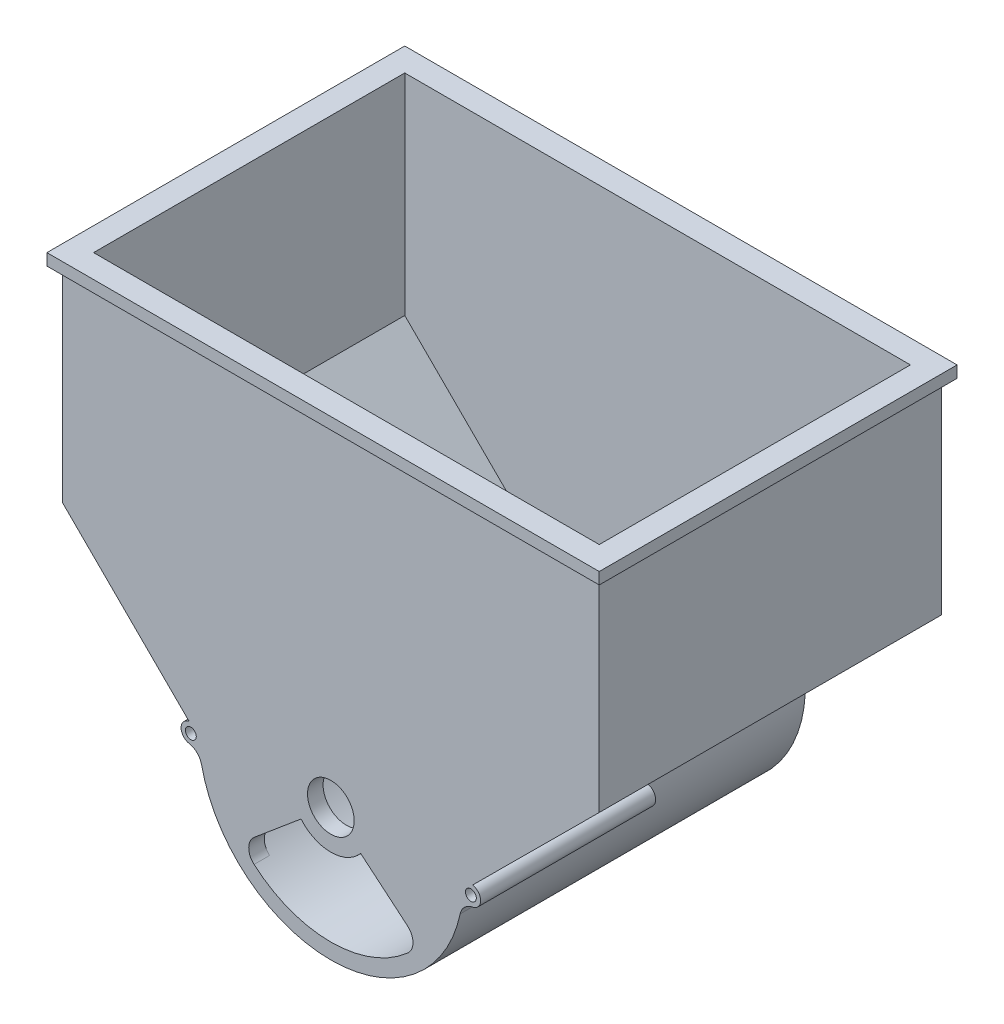
SolidWorks part; units mm, degrees
ref_plane "前基準面" through (0, 0, 0) normal (0, 0, 1) x (1, 0, 0)
ref_plane "上基準面" through (0, 0, 0) normal (0, 1, 0) x (1, 0, 0)
ref_plane "右基準面" through (0, 0, 0) normal (1, 0, 0) x (0, 0, -1)
sketch "草圖1" plane through (0, 0, 0) normal (0, 0, 1) x (1, 0, 0)
  line L0 (65, 50) -> (65, -35) construction
  line L2 (0, 0) -> (0, 50)
  line L3 (0, 50) -> (130, 50)
  line L4 (130, 0) -> (130, 50)
  line L5 (0, 0) -> (35.0004, -34.8465)
  line L6 (130, 0) -> (94.9996, -34.8465)
  line L7 (-4, -1.662) -> (-4, 54)
  line L8 (-4, 54) -> (134, 54)
  line L9 (134, -1.662) -> (134, 54)
  line L10 (134, -1.662) -> (98.965, -36.543)
  line L11 (-4, -1.662) -> (31.035, -36.543)
  arc A0 (35.0004, -34.8465) -> (94.9996, -34.8465) centre (65, -35) ccw
  arc A1 (31.035, -36.543) -> (98.965, -36.543) centre (65, -35) ccw
  dimension "D4" = 60
  dimension "D1" = 130
  dimension "D2" = 50
  dimension "D3" = 85
  dimension "D5" = 4
  dimension "D6" = 50
extrude "填料-伸長1" add sketch "草圖1" along normal blind 80
sketch "草圖2" plane through (0, 0, 80) normal (0, 0, 1) x (1, 0, 0)
  line L5 (-4, 54) -> (-4, -1.662)
  line L6 (134, 54) -> (-4, 54)
  line L7 (134, -1.662) -> (134, 54)
  line L8 (98.965, -36.543) -> (134, -1.662)
  line L9 (-4, -1.662) -> (31.035, -36.543)
  line L10 (-4, 54) -> (-4, -1.662)
  line L11 (134, 54) -> (-4, 54)
  line L12 (134, -1.662) -> (134, 54)
  line L13 (98.965, -36.543) -> (134, -1.662)
  line L14 (-4, -1.662) -> (31.035, -36.543)
  line L15 (0, 50) -> (0, 0)
  line L16 (130, 50) -> (0, 50)
  line L17 (130, 0) -> (130, 50)
  line L18 (94.9996, -34.8465) -> (130, 0)
  line L19 (0, 0) -> (35.0004, -34.8465)
  arc A1 (31.035, -36.543) -> (98.965, -36.543) centre (65, -35) ccw
  arc A2 (31.035, -36.543) -> (98.965, -36.543) centre (65, -35) ccw
  arc A3 (35.0004, -34.8465) -> (94.9996, -34.8465) centre (65, -35) ccw
  arc A4 (35.0004, -34.8465) -> (94.9996, -34.8465) centre (65, -35) ccw
  line M13 (-4, -1.662) -> (31.035, -36.543)
  arc M14 (31.035, -36.543) -> (98.965, -36.543) centre (65, -35) ccw
  line M15 (98.965, -36.543) -> (134, -1.662)
  line M16 (134, -1.662) -> (134, 54)
  line M17 (134, 54) -> (-4, 54)
  line M18 (-4, 54) -> (-4, -1.662)
  arc M19 (94.9996, -34.8465) -> (35.0004, -34.8465) centre (65, -35) cw
  line M20 (35.0004, -34.8465) -> (0, 0)
  line M21 (0, 0) -> (0, 50)
  line M22 (0, 50) -> (130, 50)
  line M23 (130, 50) -> (130, 0)
  line M24 (130, 0) -> (94.9996, -34.8465)
  dimension "D1" = 0
  dimension "D2" = 0
extrude "填料-伸長2" add sketch "草圖2" along normal blind 4 contours M18 M13 M14 M15 M16 M17 M24 M19 M20 M21 M22 M23 | M19 M24 M23 M22 M21 M20 region at (65, 52.1514, 80) region at (65, 3.9261, 80)
sketch "草圖3" plane through (0, 0, 0) normal (0, 0, -1) x (-1, 0, 0)
  line L5 (4, -1.662) -> (4, 54)
  line L6 (-31.035, -36.543) -> (4, -1.662)
  line L7 (-134, -1.662) -> (-98.965, -36.543)
  line L8 (-134, 54) -> (-134, -1.662)
  line L9 (4, 54) -> (-134, 54)
  line L10 (4, -1.662) -> (4, 54)
  line L11 (-31.035, -36.543) -> (4, -1.662)
  line L12 (-134, -1.662) -> (-98.965, -36.543)
  line L13 (-134, 54) -> (-134, -1.662)
  line L14 (4, 54) -> (-134, 54)
  arc A0 (-94.9996, -34.8465) -> (-35.0004, -34.8465) centre (-65, -35) ccw construction
  arc A1 (-98.965, -36.543) -> (-31.035, -36.543) centre (-65, -35) ccw
  arc A2 (-98.965, -36.543) -> (-31.035, -36.543) centre (-65, -35) ccw
  arc A3 (-94.9996, -34.8465) -> (-35.0004, -34.8465) centre (-65, -35) ccw
  line M7 (-31.035, -36.543) -> (4, -1.662)
  line M8 (4, -1.662) -> (4, 54)
  line M9 (4, 54) -> (-134, 54)
  line M10 (-134, 54) -> (-134, -1.662)
  line M11 (-134, -1.662) -> (-98.965, -36.543)
  arc M12 (-98.965, -36.543) -> (-31.035, -36.543) centre (-65, -35) ccw
  line M13 (0, 0) -> (-35.0004, -34.8465)
  arc M14 (-35.0004, -34.8465) -> (-94.9996, -34.8465) centre (-65, -35) cw
  line M15 (-94.9996, -34.8465) -> (-130, 0)
  line M16 (-130, 0) -> (-130, 50)
  line M17 (-130, 50) -> (0, 50)
  line M18 (0, 50) -> (0, 0)
  dimension "D1" = 0
extrude "填料-伸長3" add sketch "草圖3" along normal blind 4 contours M13 M18 M17 M16 M15 M14 | M12 M7 M8 M9 M10 M11 M18 M13 M14 M15 M16 M17 region at (14.8218, -17.7925, 0) region at (65, 3.9261, 0)
sketch "草圖4" plane through (0, 54, 0) normal (0, 1, 0) x (1, 0, 0)
  line L0 (-4, -84) -> (-4, 4) construction
  line L1 (-4, 4) -> (134, 4)
  line L2 (-4, 4) -> (-4, -84)
  line L3 (-4, -84) -> (134, -84)
  line L4 (134, 4) -> (134, -84)
  line L5 (-4, 4) -> (134, 4) construction
  line L6 (0, 0) -> (130, 0)
  line L7 (130, 0) -> (130, -80)
  line L8 (0, -80) -> (130, -80)
  line L9 (0, 0) -> (0, -80)
  dimension "D1" = 4
extrude "除料-伸長1" cut sketch "草圖4" against normal blind 4 contours L6 L9 L8 L7 region at (65, 54, 40)
sketch "草圖5" plane through (0, 0, 84) normal (0, 0, 1) x (1, 0, 0)
  line L0 (65, 54) -> (65, -69) construction
  line L1 (134, 54) -> (-4, 54) construction
  arc A0 (31.035, -36.543) -> (98.965, -36.543) centre (65, -35) ccw construction
  circle A1 centre (65, -35) radius 6
  dimension "D1" = 12
extrude "除料-伸長2" cut sketch "草圖5" against normal up to surface (88 mm away) up to face at (65, -0.1445, -4)
sketch "草圖6" plane through (0, 0, 84) normal (0, 0, 1) x (1, 0, 0)
  line L0 (65, -35) -> (42.0187, -54.2836)
  line L1 (65, -35) -> (87.9813, -54.2836)
  line L2 (65, 54) -> (65, -69) construction
  line L3 (134, 54) -> (-4, 54) construction
  arc A0 (42.0187, -54.2836) -> (87.9813, -54.2836) centre (65, -35) ccw
  arc A1 (31.035, -36.543) -> (98.965, -36.543) centre (65, -35) ccw construction
  arc A2 (57.3396, -41.4279) -> (72.6604, -41.4279) centre (65, -35) ccw
  dimension "D1" = 4
  dimension "D2" = 20
  dimension "D3" = 50
  dimension "D4" = 50
extrude "除料-伸長3" cut sketch "草圖6" against normal up to surface (4 mm away) contours L2 A2 L0 A0 | A2 L2 A0 L1 region at (56.1311, -54.0195, 84) region at (73.8689, -54.0195, 84) up to face at (71, -35, 80)
sketch "草圖7" plane through (0, 0, -4) normal (0, 0, -1) x (-1, 0, 0)
  line L0 (-65, 54) -> (-65, -69) construction
  line L1 (4, 54) -> (-134, 54) construction
  circle A0 centre (-65, -43) radius 21
  circle A1 centre (-65, -35) radius 6 construction
  arc A2 (-98.965, -36.543) -> (-31.035, -36.543) centre (-65, -35) ccw construction
  dimension "D1" = 42
  dimension "D2" = 8
extrude "填料-伸長4" add sketch "草圖7" along normal blind 1
sketch "草圖9" plane through (0, 0, -5) normal (0, 0, -1) x (-1, 0, 0)
  line L0 (-65, -22) -> (-65, -64) construction
  line L1 (-86, -43) -> (-44, -43) construction
  circle A0 centre (-65, -35) radius 4.6
  circle A1 centre (-65, -43) radius 21
  circle A2 centre (-65, -43) radius 21
  circle A3 centre (-82.5, -43) radius 1.35
  circle A4 centre (-47.5, -43) radius 1.35
  dimension "D2" = 9.2
  dimension "D3" = 2.7
  dimension "D4" = 17.5
  dimension "D5" = 8
  dimension "D1" = 0
extrude "除料-伸長5" cut sketch "草圖9" against normal up to next contours A0 | A3 | A4 region at (65, -35, -5) region at (82.5, -43, -5) region at (47.5, -43, -5)
ref_plane "平面1" through (65, 0, 0) normal (1, 0, 0) x (0, 0, -1)
sketch "草圖10" plane through (65, 0, 0) normal (1, 0, 0) x (0, 0, -1)
  line L0 (-84, -69) -> (-84, 0) construction
  line L1 (-84, 28.7653) -> (-59, 1)
  line L3 (-84, 1) -> (-84, 28.7653)
  line L4 (-83, 26.1602) -> (-60.3456, 1)
  line L5 (-60.3456, 1) -> (-83, 1)
  line L6 (-83, 1) -> (-83, 26.1602)
  line L7 (-83, 1) -> (-84, 1)
  line L8 (-60.3456, 1) -> (-59, 1)
  line L9 (-84, 28.7653) -> (-58.0996, 0) construction
  line L10 (-58.0996, 0) -> (-84, 0) construction
  line L11 (-84, 1) -> (-84, 71.0976) construction
  line L12 (-84, 0) -> (-84, 28.7653) construction
  line L14 (-84, -1.662) -> (-84, 54) construction
  dimension "D1" = 1
  dimension "D2" = 42
  dimension "D3" = 70
  dimension "D4" = 25
extrude "填料-伸長5" add sketch "草圖10" along normal up to surface and the other way up to surface contours L4 L8 L1 L3 L7 L6 region at (65, 14.6327, 71.7777) up to face at (130, 27, 40) other way up to face at (0, 27, 40)
sketch "草圖11" plane through (0, 0, 84) normal (0, 0, 1) x (1, 0, 0)
  line L0 (-4, -1.662) -> (31.035, -36.543)
  line L1 (31.035, -36.543) -> (-4, -36.543)
  line L2 (-4, -36.543) -> (-4, -1.662)
  line L3 (134, -1.662) -> (98.965, -36.543)
  line L4 (98.965, -36.543) -> (134, -36.543)
  line L5 (134, -36.543) -> (134, -1.662)
extrude "除料-伸長6" [suppressed] cut sketch "草圖11" against normal up to surface (88 mm away)
sketch "草圖12" plane through (0, 54, 0) normal (0, 1, 0) x (1, 0, 0)
  line L0 (-4, -84) -> (-4, 4) construction
  line L1 (-6, 6) -> (136, 6)
  line L2 (-6, 6) -> (-6, -86)
  line L3 (-6, -86) -> (136, -86)
  line L4 (136, 6) -> (136, -86)
  line L5 (-4, 4) -> (134, 4) construction
  line L6 (134, -84) -> (134, 4) construction
  line L7 (134, -84) -> (-4, -84) construction
  line L9 (-4, 4) -> (134, 4)
  line L10 (-4, 4) -> (-4, -84)
  line L11 (-4, -84) -> (134, -84)
  line L12 (134, 4) -> (134, -84)
  dimension "D1" = 2
  dimension "D2" = 2
  dimension "D3" = 2
  dimension "D4" = 2
extrude "填料-伸長6" add sketch "草圖12" against normal blind 3
chamfer "導角1" distance 1 angle 45 1 edges at (44, -43, -4)
sketch "草圖13" plane through (0, 0, 84) normal (0, 0, 1) x (1, 0, 0)
  line L0 (31.035, -36.543) -> (98.965, -36.543) construction
  line L1 (29, -36.543) -> (101, -36.543) construction
  line L2 (65, -69) -> (65, 51) construction
  line L3 (-4, 51) -> (134, 51) construction
  arc A0 (29.0868, -34.0445) -> (29.0272, -35.1432) centre (65, -36.543) ccw
  circle A2 centre (29, -36.543) radius 2.5
  circle A3 centre (29, -36.543) radius 1.4
  arc A4 (29.0272, -37.9427) -> (101, -36.543) centre (65, -36.543) ccw
  arc A5 (31.035, -36.543) -> (98.965, -36.543) centre (65, -35) ccw construction
  circle A6 centre (101, -36.543) radius 1.4
  circle A7 centre (101, -36.543) radius 2.5
  line M9 (-4, -1.662) -> (31.035, -36.543)
  arc M10 (31.035, -36.543) -> (98.965, -36.543) centre (65, -35) ccw
  line M11 (98.965, -36.543) -> (134, -1.662)
  dimension "D1" = 72
  dimension "D2" = 2.8
  dimension "D3" = 5
extrude "填料-伸長7" add sketch "草圖13" against normal blind 45 contours A3 A4 A2 A0 M10 M9 | A4 A3 A0 A2 M9 | A2 A0 M10 M9 | A0 A2 M9 | A7 A6 M11 M10 | A7 M10 M11 region at (30.466, -35.4427, 84) region at (28.8982, -34.2261, 84) region at (30.137, -37.5815, 84) region at (28.9836, -34.8543, 84) region at (98.9961, -37.2095, 84) region at (99.6002, -35.3913, 84)
fillet "圓角1" radius 4 2 edges at (42.0187, -54.2836, 82) (87.9813, -54.2836, 82)
fillet "圓角2" radius 4 2 edges at (31.121, -37.8663, 61.5) (98.879, -37.8663, 61.5)
